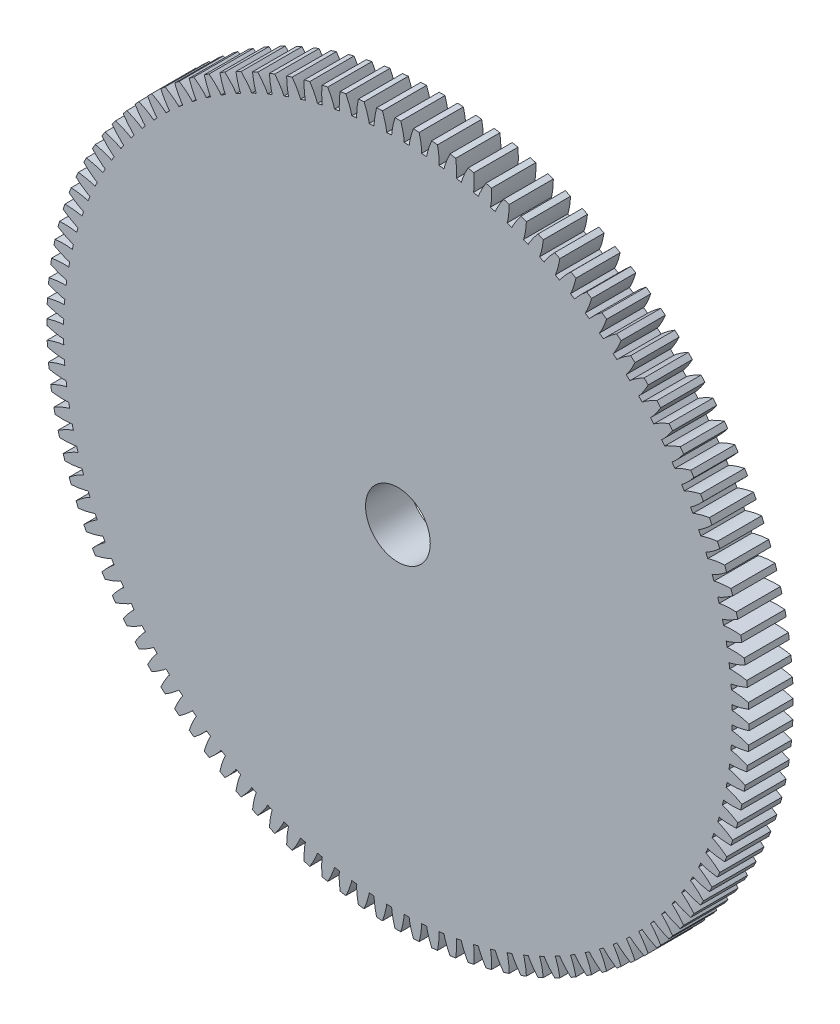
SolidWorks part; units mm, degrees
material "Brass"
ref_plane "Front Plane" through (0, 0, 0) normal (0, 0, 1) x (1, 0, 0)
ref_plane "Top Plane" through (0, 0, 0) normal (0, 1, 0) x (1, 0, 0)
ref_plane "Right Plane" through (0, 0, 0) normal (1, 0, 0) x (0, 0, -1)
sketch "Sketch1" plane through (0, 0, 0) normal (0, 0, 1) x (1, 0, 0)
  circle A0 centre (0, 0) radius 51.6467
extrude "Boss-Extrude1" add sketch "Sketch1" along normal blind 6.5
sketch "Sketch2" plane through (0, 0, 0) normal (0, 0, 1) x (1, 0, 0)
  circle A0 centre (0, 0) radius 4.7625
  dimension "D1" = 9.525
extrude "Cut-Extrude2" cut sketch "Sketch2" against normal blind 8.5 and the other way blind 8.5
sketch "Sketch3" plane through (0, 0, 0) normal (0, 0, 1) x (1, 0, 0)
  spline S0 degree 4 poles (49.1734, 0.9164) (49.1838, 0.9166) (49.2037, 0.9164) (49.236, 0.9157) (49.2811, 0.9138) (49.3345, 0.9109) (49.3975, 0.9065) (49.4669, 0.9007) (49.5426, 0.8933) (49.6181, 0.8849) (49.6937, 0.8757) (49.769, 0.8656) (49.8604, 0.8525) (49.9703, 0.8355) (50.099, 0.8136) (50.2454, 0.7864) (50.3952, 0.7562) (50.5429, 0.7245) (50.6927, 0.69) (50.8381, 0.655) (50.9896, 0.6161) (51.1298, 0.579) (51.2875, 0.5348) (51.415, 0.4982) (51.584, 0.4471) (51.6841, 0.416) (51.8014, 0.3786) (51.8537, 0.3614) (51.8859, 0.3509) knots 0 0 0 0 0 0.015084 0.028532 0.04661 0.064855 0.092111 0.119476 0.146842 0.174209 0.201575 0.228941 0.256307 0.307035 0.361767 0.4165 0.471232 0.525964 0.580697 0.635429 0.690161 0.744894 0.799626 0.854358 0.909091 0.954545 1 1 1 1 1 construction
  spline S1 degree 4 poles (49.1734, 0.9164) (49.1838, 0.9166) (49.2037, 0.9164) (49.236, 0.9157) (49.2811, 0.9138) (49.3345, 0.9109) (49.3975, 0.9065) (49.4669, 0.9007) (49.5426, 0.8933) (49.6181, 0.8849) (49.6937, 0.8757) (49.769, 0.8656) (49.8604, 0.8525) (49.9703, 0.8355) (50.099, 0.8136) (50.2454, 0.7864) (50.3952, 0.7562) (50.5429, 0.7245) (50.6927, 0.69) (50.8381, 0.655) (50.9896, 0.6161) (51.1298, 0.579) (51.2875, 0.5348) (51.415, 0.4982) (51.5474, 0.4582) (51.6119, 0.4383) (51.6449, 0.428) knots 0 0 0 0 0 0.015084 0.028532 0.04661 0.064855 0.092111 0.119476 0.146842 0.174209 0.201575 0.228941 0.256307 0.307035 0.361767 0.4165 0.471232 0.525964 0.580697 0.635429 0.690161 0.744894 0.799626 0.854358 0.909091 0.909091 0.909091 0.909091 0.909091
  spline S2 degree 4 poles (49.1539, 1.6583) (49.1644, 1.6588) (49.1842, 1.66) (49.2165, 1.6624) (49.2614, 1.6666) (49.3146, 1.6723) (49.3773, 1.68) (49.4463, 1.6894) (49.5214, 1.7008) (49.5965, 1.7131) (49.6714, 1.7263) (49.7461, 1.7403) (49.8367, 1.7581) (49.9455, 1.7809) (50.0729, 1.8095) (50.2177, 1.8443) (50.3657, 1.8823) (50.5116, 1.9217) (50.6594, 1.964) (50.8027, 2.0066) (50.952, 2.0533) (51.09, 2.0977) (51.2452, 2.1502) (51.3706, 2.1933) (51.5367, 2.2532) (51.635, 2.2895) (51.7503, 2.333) (51.8016, 2.3529) (51.8332, 2.3651) knots 0 0 0 0 0 0.015084 0.028532 0.04661 0.064855 0.092111 0.119476 0.146842 0.174209 0.201575 0.228941 0.256307 0.307035 0.361767 0.4165 0.471232 0.525964 0.580697 0.635429 0.690161 0.744894 0.799626 0.854358 0.909091 0.954545 1 1 1 1 1 construction
  spline S3 degree 4 poles (49.1539, 1.6583) (49.1644, 1.6588) (49.1842, 1.66) (49.2165, 1.6624) (49.2614, 1.6666) (49.3146, 1.6723) (49.3773, 1.68) (49.4463, 1.6894) (49.5214, 1.7008) (49.5965, 1.7131) (49.6714, 1.7263) (49.7461, 1.7403) (49.8367, 1.7581) (49.9455, 1.7809) (50.0729, 1.8095) (50.2177, 1.8443) (50.3657, 1.8823) (50.5116, 1.9217) (50.6594, 1.964) (50.8027, 2.0066) (50.952, 2.0533) (51.09, 2.0977) (51.2452, 2.1502) (51.3706, 2.1933) (51.5007, 2.2403) (51.5641, 2.2634) (51.5965, 2.2754) knots 0 0 0 0 0 0.015084 0.028532 0.04661 0.064855 0.092111 0.119476 0.146842 0.174209 0.201575 0.228941 0.256307 0.307035 0.361767 0.4165 0.471232 0.525964 0.580697 0.635429 0.690161 0.744894 0.799626 0.854358 0.909091 0.909091 0.909091 0.909091 0.909091
  spline S4 degree 4 poles (49.152, 1.7331) (49.1521, 1.7275) (49.1524, 1.7162) (49.1528, 1.7032) (49.1537, 1.6661) (49.1542, 1.6496) (49.1554, 1.6026) (49.1561, 1.5744) (49.1572, 1.5339) (49.158, 1.5022) (49.1589, 1.4673) (49.1598, 1.4358) (49.1606, 1.4032) (49.1615, 1.3704) (49.1623, 1.3377) (49.1632, 1.3038) (49.1641, 1.2685) (49.1651, 1.2321) (49.1661, 1.1947) (49.1671, 1.1572) (49.168, 1.1226) (49.1689, 1.0853) (49.1698, 1.0523) (49.1709, 1.0096) (49.1717, 0.9804) (49.1731, 0.927) (49.1735, 0.9094) (49.1745, 0.8714) (49.1749, 0.857) (49.1752, 0.847) (49.1753, 0.8418) knots 0 0 0 0 0 0.022088 0.044177 0.083333 0.119319 0.159813 0.201093 0.243304 0.280291 0.314751 0.350761 0.388774 0.424594 0.463227 0.497138 0.541352 0.583276 0.626202 0.666552 0.706902 0.743676 0.7856 0.828955 0.87417 0.916667 0.958835 0.979418 1 1 1 1 1 construction
  spline S5 degree 4 poles (49.1539, 1.6583) (49.1541, 1.6517) (49.1545, 1.6378) (49.1554, 1.6026) (49.1561, 1.5744) (49.1572, 1.5339) (49.158, 1.5022) (49.1589, 1.4673) (49.1598, 1.4358) (49.1606, 1.4032) (49.1615, 1.3704) (49.1623, 1.3377) (49.1632, 1.3038) (49.1641, 1.2685) (49.1651, 1.2321) (49.1661, 1.1947) (49.1671, 1.1572) (49.168, 1.1226) (49.1689, 1.0853) (49.1698, 1.0523) (49.1709, 1.0096) (49.1717, 0.9804) (49.1727, 0.94) (49.1732, 0.9243) (49.1734, 0.9164) knots 0.083333 0.083333 0.083333 0.083333 0.083333 0.119319 0.159813 0.201093 0.243304 0.280291 0.314751 0.350761 0.388774 0.424594 0.463227 0.497138 0.541352 0.583276 0.626202 0.666552 0.706902 0.743676 0.7856 0.828955 0.87417 0.916667 0.916667 0.916667 0.916667 0.916667
  spline S6 degree 4 poles (50.8043, 0.4211) (50.864, 0.4216) (50.9794, 0.4225) (51.1316, 0.4238) (51.5629, 0.4274) (51.7496, 0.4289) (52.3065, 0.4335) (52.6262, 0.4362) (53.0785, 0.4399) (53.4484, 0.443) (53.8676, 0.4465) (54.2464, 0.4496) (54.6546, 0.453) (55.0383, 0.4562) (55.4322, 0.4594) (55.8223, 0.4627) (56.2055, 0.4658) (56.6028, 0.4691) (56.9958, 0.4724) (57.4001, 0.4757) (57.7912, 0.479) (58.2102, 0.4825) (58.5784, 0.4855) (59.0365, 0.4893) (59.3484, 0.4919) (59.8904, 0.4964) (60.0774, 0.4979) (60.499, 0.5014) (60.6501, 0.5027) (60.7751, 0.5037) (60.8382, 0.5042) knots 0 0 0 0 0 0.020582 0.041165 0.083333 0.123922 0.164487 0.203919 0.245641 0.283463 0.324863 0.363448 0.401438 0.443624 0.479586 0.519794 0.557378 0.596758 0.637386 0.678142 0.716036 0.757316 0.79719 0.837516 0.878097 0.916667 0.955572 0.977786 1 1 1 1 1 construction
  spline S7 degree 4 poles (51.6449, 0.428) (51.7297, 0.4287) (51.8939, 0.4301) (52.3065, 0.4335) (52.6262, 0.4362) (53.0785, 0.4399) (53.4484, 0.443) (53.8676, 0.4465) (54.2464, 0.4496) (54.6546, 0.453) (55.0383, 0.4562) (55.4322, 0.4594) (55.8223, 0.4627) (56.2055, 0.4658) (56.6028, 0.4691) (56.9958, 0.4724) (57.4001, 0.4757) (57.7912, 0.479) (58.2102, 0.4825) (58.5784, 0.4855) (59.0365, 0.4893) (59.3484, 0.4919) (59.7573, 0.4953) (59.9173, 0.4966) (59.9978, 0.4973) knots 0.083333 0.083333 0.083333 0.083333 0.083333 0.123922 0.164487 0.203919 0.245641 0.283463 0.324863 0.363448 0.401438 0.443624 0.479586 0.519794 0.557378 0.596758 0.637386 0.678142 0.716036 0.757316 0.79719 0.837516 0.878097 0.916667 0.916667 0.916667 0.916667 0.916667
  spline S8 degree 4 poles (59.9992, 0.2811) (59.9991, 0.2966) (59.999, 0.3264) (59.9988, 0.3667) (59.998, 0.4759) (59.9976, 0.5237) (59.9963, 0.6646) (59.9953, 0.7445) (59.9938, 0.8601) (59.9923, 0.9543) (59.9905, 1.0614) (59.9887, 1.1607) (59.9866, 1.2646) (59.9844, 1.3658) (59.9819, 1.4686) (59.9794, 1.5706) (59.9766, 1.6727) (59.9736, 1.7754) (59.9706, 1.8766) (59.9672, 1.9805) (59.9639, 2.0797) (59.96, 2.1868) (59.9566, 2.2809) (59.952, 2.3964) (59.9488, 2.4763) (59.9428, 2.617) (59.9407, 2.6648) (59.9358, 2.7739) (59.9338, 2.8142) (59.9324, 2.844) (59.9317, 2.8594) knots 0 0 0 0 0 0.020959 0.041918 0.083333 0.123016 0.162698 0.202381 0.242063 0.281746 0.321429 0.361111 0.400794 0.440476 0.480159 0.519841 0.559524 0.599206 0.638889 0.678571 0.718254 0.757937 0.797619 0.837302 0.876984 0.916667 0.958082 0.979041 1 1 1 1 1 construction
  spline S9 degree 4 poles (59.9978, 0.4973) (59.9976, 0.5186) (59.9973, 0.5601) (59.9963, 0.6646) (59.9953, 0.7445) (59.9938, 0.8601) (59.9923, 0.9543) (59.9905, 1.0614) (59.9887, 1.1607) (59.9866, 1.2646) (59.9844, 1.3658) (59.9819, 1.4686) (59.9794, 1.5706) (59.9766, 1.6727) (59.9736, 1.7754) (59.9706, 1.8766) (59.9672, 1.9805) (59.9639, 2.0797) (59.96, 2.1868) (59.9566, 2.2809) (59.952, 2.3964) (59.9488, 2.4763) (59.9444, 2.5807) (59.9426, 2.6222) (59.9416, 2.6434) knots 0.083333 0.083333 0.083333 0.083333 0.083333 0.123016 0.162698 0.202381 0.242063 0.281746 0.321429 0.361111 0.400794 0.440476 0.480159 0.519841 0.559524 0.599206 0.638889 0.678571 0.718254 0.757937 0.797619 0.837302 0.876984 0.916667 0.916667 0.916667 0.916667 0.916667
  spline S10 degree 4 poles (60.7813, 2.6805) (60.7233, 2.6779) (60.6112, 2.673) (60.4593, 2.6663) (60.0264, 2.6472) (59.8505, 2.6394) (59.3125, 2.6157) (59.0208, 2.6028) (58.6061, 2.5846) (58.2603, 2.5693) (57.8595, 2.5516) (57.496, 2.5356) (57.0992, 2.5181) (56.7297, 2.5018) (56.3678, 2.4858) (56.0013, 2.4697) (55.6349, 2.4535) (55.2589, 2.4369) (54.8708, 2.4198) (54.4874, 2.4029) (54.084, 2.3851) (53.7043, 2.3684) (53.2954, 2.3503) (52.937, 2.3345) (52.5215, 2.3162) (52.2196, 2.3029) (51.696, 2.2798) (51.481, 2.2703) (51.015, 2.2498) (50.8906, 2.2443) (50.7566, 2.2384) knots 0 0 0 0 0 0.02008 0.040161 0.083333 0.123261 0.159319 0.197812 0.233027 0.26907 0.309878 0.349805 0.383268 0.424652 0.459253 0.493239 0.530412 0.57034 0.610222 0.64719 0.685114 0.729048 0.765971 0.80369 0.838967 0.877741 0.916667 0.958333 1 1 1 1 1 construction
  spline S11 degree 4 poles (59.9416, 2.6434) (59.8583, 2.6398) (59.7031, 2.6329) (59.3125, 2.6157) (59.0208, 2.6028) (58.6061, 2.5846) (58.2603, 2.5693) (57.8595, 2.5516) (57.496, 2.5356) (57.0992, 2.5181) (56.7297, 2.5018) (56.3678, 2.4858) (56.0013, 2.4697) (55.6349, 2.4535) (55.2589, 2.4369) (54.8708, 2.4198) (54.4874, 2.4029) (54.084, 2.3851) (53.7043, 2.3684) (53.2954, 2.3503) (52.937, 2.3345) (52.5215, 2.3162) (52.2196, 2.3029) (51.8371, 2.286) (51.6777, 2.279) (51.5965, 2.2754) knots 0.083333 0.083333 0.083333 0.083333 0.083333 0.123261 0.159319 0.197812 0.233027 0.26907 0.309878 0.349805 0.383268 0.424652 0.459253 0.493239 0.530412 0.57034 0.610222 0.64719 0.685114 0.729048 0.765971 0.80369 0.838967 0.877741 0.916667 0.916667 0.916667 0.916667 0.916667
extrude "Cut-Extrude4" cut sketch "Sketch3" against normal blind 7.5 and the other way blind 7.5
ref_axis "Axis1" through (0, 0, -0.325) along (0, 0, 1)
pattern_circular "CirPattern1" count 120 over 360 about axis through (0, 0, -0.325) along (0, 0, 1) of "Cut-Extrude4"
equation "\"TrigProbe\"= cos(60)"
equation "\"SqrProbe\"= sqr(2)"
equation "\"AtnProbe\"= atn(1)"
equation "\"ToothCount\" = 120"
equation "\"DP\"= 30"
equation "\"PA\"= 14.5"
equation "\"PArad\"= \"PA\" * 3.14159265358979 / 180"
equation "\"Rb\"= \"ToothCount\" / \"DP\" * cos(\"PA\") / 2"
equation "\"Ra\"= (\"ToothCount\" + 2) / \"DP\" / 2"
equation "\"Tmax\"= sqr(\"Ra\" * \"Ra\" / (\"Rb\" * \"Rb\") - 1)"
equation "\"Delta\"= 3.14159265358979 / (2 * \"ToothCount\") + tan(\"PA\") - \"PArad\""
equation "\"Gamma\"= 2 * 3.14159265358979 / \"ToothCount\""
equation "\"ThetaL\"= atn(\"Tmax\") * 3.14159265358979 / 180 - \"Tmax\" + \"Delta\""
equation "\"ThetaU\"= \"Tmax\" - atn(\"Tmax\") * 3.14159265358979 / 180 - \"Delta\" + \"Gamma\""
equation "\"D1@Sketch1\" = 2 * \"Ra\""
equation "\"BoreDia\" = 0.375"
equation "\"D1@Sketch2\" = \"BoreDia\""
equation "\"D1@CirPattern1\" = \"ToothCount\""
